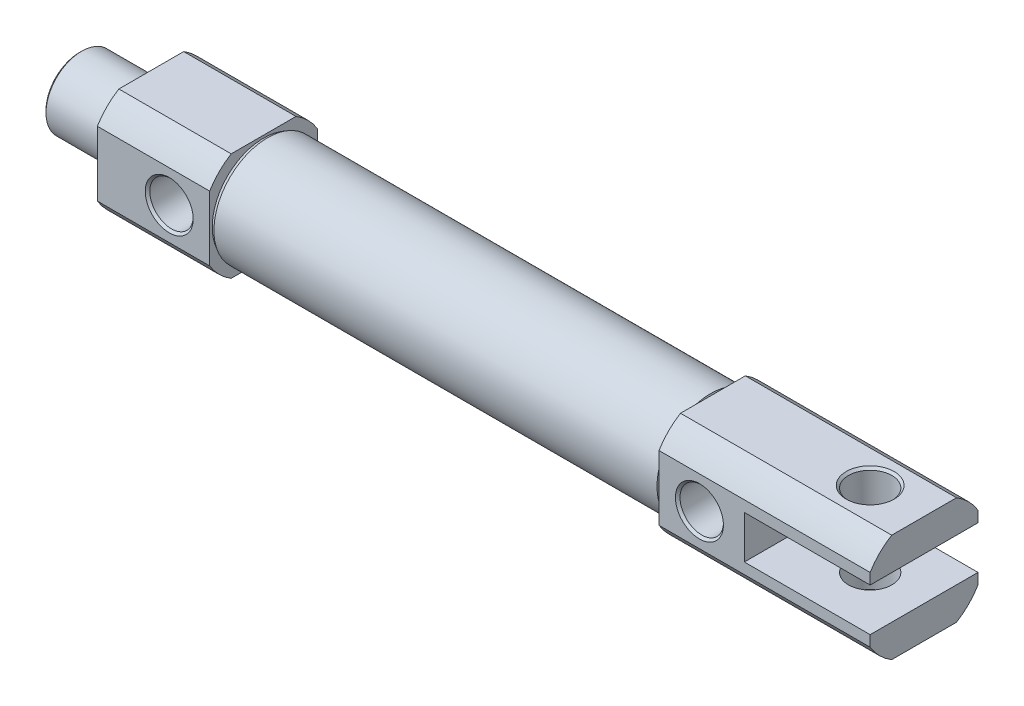
SolidWorks part; units mm, degrees
ref_plane "Front Plane" through (0, 0, 0) normal (0, 0, 1) x (1, 0, 0)
ref_plane "Top Plane" through (0, 0, 0) normal (0, 1, 0) x (1, 0, 0)
ref_plane "Right Plane" through (0, 0, 0) normal (1, 0, 0) x (0, 0, -1)
sketch "Sketch1" plane through (0, 0, 0) normal (1, 0, 0) x (0, 0, -1)
  circle A0 centre (0, 0) radius 5
  circle A1 centre (0, 0) radius 5.97
  dimension "D1" = 10
  dimension "D2" = 11.94
extrude "Boss-Extrude1" add sketch "Sketch1" along normal mid plane 30.4 contours A0 region at (0, 0, 0)
extrude "Boss-Extrude2" add sketch "Sketch1<3>" along normal mid plane 50
sketch "Sketch1<3>" plane through (0, 0, 0) normal (1, 0, 0) x (0, 0, -1) same geometry as "Sketch1"
chamfer "Chamfer1" distance 0.254 angle 60 1 edges at (25, 0, -5.97) first distance on face at (25, 0, -5.97)
chamfer "Chamfer2" distance 0.254 angle 60 1 edges at (-25, 0, -5.97) first distance on face at (-25, 0, -5.97)
sketch "Sketch2" plane through (25, 0, 0) normal (1, 0, 0) x (0, 0, -1)
  line L1 (6, -6) -> (-6, -6)
  line L2 (6, -6) -> (6, 6)
  line L3 (6, 6) -> (-6, 6)
  line L4 (-6, -6) -> (-6, 6)
  line L5 (6, -6) -> (-6, 6) construction
  line L6 (6, 6) -> (-6, -6) construction
  circle A0 centre (0, 0) radius 7
  point P0 (0, 0)
  dimension "D3" = 14
  dimension "D1" = 12
  dimension "D2" = 12
sketch "Sketch3" plane through (25, 0, 0) normal (1, 0, 0) x (0, 0, -1)
  line L0 (-6, 3.6055) -> (-6, -3.6055)
  line L1 (6, 3.6055) -> (6, -3.6055)
  line L2 (-3.6055, 6) -> (3.6055, 6)
  line L3 (-3.6055, -6) -> (3.6055, -6)
  line L4 (6, -6) -> (6, 6) construction
  line L5 (6, 6) -> (-6, 6) construction
  line L6 (-6, -6) -> (-6, 6) construction
  line L7 (6, -6) -> (-6, -6) construction
  arc A0 (-6, 3.6055) -> (-3.6055, 6) centre (0, 0) cw
  arc A1 (6, 3.6055) -> (3.6055, 6) centre (0, 0) ccw
  arc A2 (6, -3.6055) -> (3.6055, -6) centre (0, 0) cw
  arc A3 (-6, -3.6055) -> (-3.6055, -6) centre (0, 0) ccw
  circle A4 centre (0, 0) radius 7 construction
extrude "Boss-Extrude3" add sketch "Sketch3" along normal blind 23.5001
sketch "Sketch5" plane through (0, 6, 0) normal (0, 1, 0) x (1, 0, 0)
  line L0 (48.5001, 3.6055) -> (48.5001, -3.6055) construction
  circle A0 centre (42.5001, 0) radius 2.415
  dimension "D2" = 4.8301
  dimension "D1" = 6
extrude "Cut-Extrude2" cut sketch "Sketch5" against normal through all
sketch "Sketch6" plane through (0, 0, 6) normal (0, 0, 1) x (1, 0, 0)
  line L0 (48.5001, 3.6055) -> (48.5001, -3.6055) construction
  line L1 (34.5001, -2.39) -> (48.5001, -2.39)
  line L2 (34.5001, -2.39) -> (34.5001, 2.39)
  line L3 (34.5001, 2.39) -> (48.5001, 2.39)
  line L4 (48.5001, -2.39) -> (48.5001, 2.39)
  line L5 (34.5001, -2.39) -> (48.5001, 2.39) construction
  line L6 (34.5001, 2.39) -> (48.5001, -2.39) construction
  point P0 (41.5001, 0)
  dimension "D1" = 14
  dimension "D2" = 4.78
extrude "Cut-Extrude3" cut sketch "Sketch6" against normal through all
extrude "Boss-Extrude4" add sketch "Sketch3<2>" against normal blind 12.5001 from surface starting at face at (-25, 0, -5.716)
sketch "Sketch3<2>" plane through (25, 0, 0) normal (1, 0, 0) x (0, 0, -1) same geometry as "Sketch3"
sketch "Sketch4" plane through (0, 0, 6) normal (0, 0, 1) x (1, 0, 0)
  line L0 (25, 3.6055) -> (25, -3.6055) construction
  line L1 (-25, 3.6055) -> (-25, -3.6055) construction
  circle A0 centre (29.5001, 0) radius 2.415
  circle A1 centre (-29.5001, 0) radius 2.415
  dimension "D2" = 4.8301
  dimension "D1" = 4.5001
  dimension "D3" = 4.5001
extrude "Cut-Extrude4" cut sketch "Sketch4" against normal blind 6
sketch "Sketch8" plane through (-37.5001, 0, 0) normal (-1, 0, 0) x (0, 0, 1)
  circle A0 centre (0, 0) radius 3.9688
  circle A1 centre (0, 0) radius 2.1827
  dimension "D1" = 4.3655
  dimension "D2" = 7.9375
extrude "Boss-Extrude5" add sketch "Sketch8" along normal blind 8
chamfer "Chamfer5" distance 0.254 angle 45 6 edges at (42.5001, -6, 2.415) (42.5001, 6, 2.415) (31.9152, 0, 6) (-27.0851, 0, 6) (-45.5001, 0, 3.9688) (-45.5001, 0, 2.1827)
equation "\"D2@Sketch2\"=\"D1@Sketch2\""
